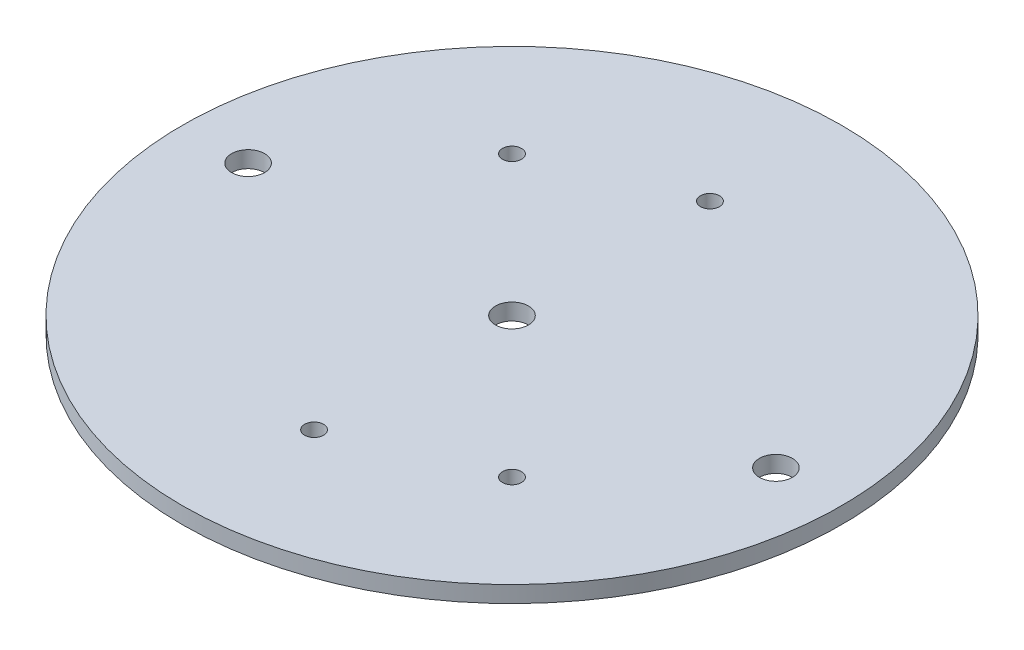
SolidWorks part; units mm, degrees
ref_plane "Front Plane" through (0, 0, 0) normal (0, 0, 1) x (1, 0, 0)
ref_plane "Top Plane" through (0, 0, 0) normal (0, 1, 0) x (1, 0, 0)
ref_plane "Right Plane" through (0, 0, 0) normal (1, 0, 0) x (0, 0, -1)
sketch "Sketch2" plane through (0, 0, 0) normal (0, 1, 0) x (1, 0, 0)
  line L0 (-50.8, 0) -> (50.8, 0) construction
  line L1 (0, -38.1) -> (0, 38.1) construction
  line L2 (-26.9408, 26.9408) -> (26.9408, -26.9408) construction
  circle A0 centre (0, 0) radius 63.4365
  circle A1 centre (-50.8, 0) radius 3.175
  circle A2 centre (50.8, 0) radius 3.175
  circle A3 centre (0, 0) radius 3.175
  circle A4 centre (0, 38.1) radius 1.8288
  circle A5 centre (0, -38.1) radius 1.8288
  circle A8 centre (-26.9408, 26.9408) radius 1.8288
  circle A9 centre (26.9408, -26.9408) radius 1.8288
  point P6 (0, 0)
  point P12 (0, 0)
  point P17 (0, 0)
  point P18 (0, 0)
  dimension "D1" = 126.873
  dimension "D3" = 6.35
  dimension "D4" = 6.35
  dimension "D5" = 3.6576
  dimension "D6" = 76.2
  dimension "D8" = 45
  dimension "D7" = 76.2
  dimension "D2" = 101.6
extrude "Boss-Extrude1" add sketch "Sketch2" along normal blind 3.175
